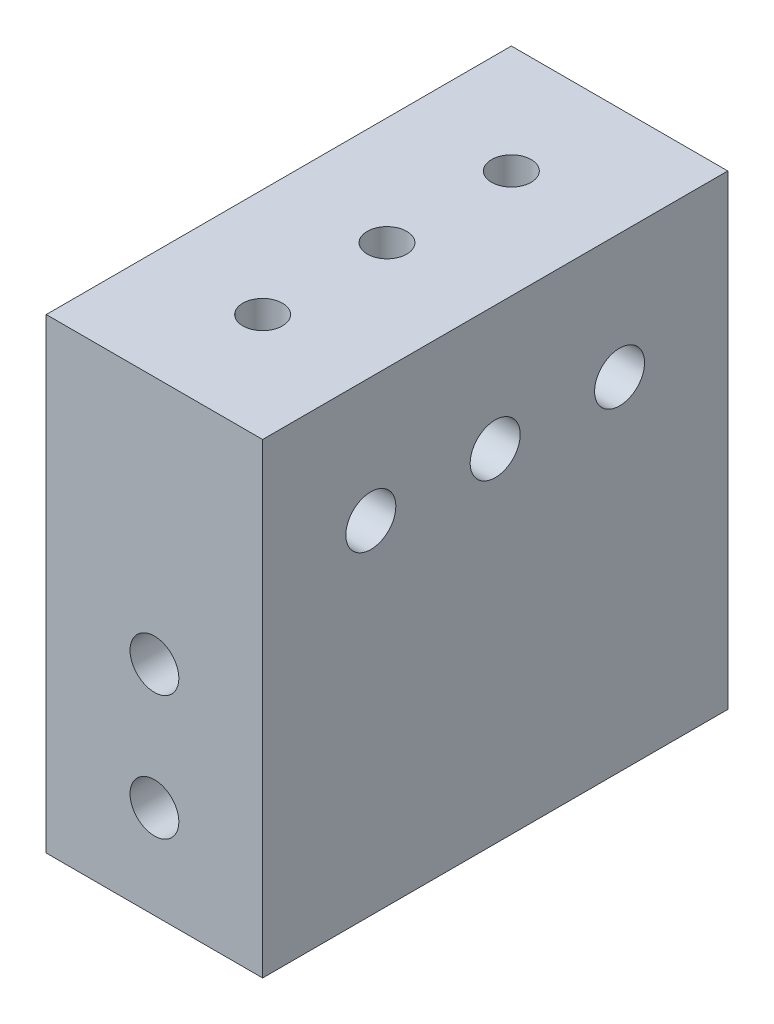
SolidWorks part; units mm, degrees
other "Markup1"
sketch "Sketch3" plane through (12.6365, 38.1, -23.749) normal (0.9027, 0.4189, -0.0984) x (-0.0151, -0.1977, -0.9801)
sketch "Sketch7" plane through (11.049, 23.8125, -23.749) normal (0.9027, 0.4189, -0.0984) x (-0.0151, -0.1977, -0.9801)
sketch "Sketch9" plane through (11.049, 23.8125, -23.749) normal (0.9027, 0.4189, -0.0984) x (-0.0151, -0.1977, -0.9801)
sketch "Sketch12" plane through (11.049, 23.8125, -23.749) normal (0.9027, 0.4189, -0.0984) x (-0.0151, -0.1977, -0.9801)
other "Markup2"
sketch "Sketch4" plane through (12.6365, 38.1, -23.749) normal (0.9027, 0.4189, -0.0984) x (-0.0151, -0.1977, -0.9801)
sketch "Sketch8" plane through (11.049, 23.8125, -23.749) normal (0.9027, 0.4189, -0.0984) x (-0.0151, -0.1977, -0.9801)
sketch "Sketch10" plane through (11.049, 23.8125, -23.749) normal (0.9027, 0.4189, -0.0984) x (-0.0151, -0.1977, -0.9801)
sketch "Sketch13" plane through (11.049, 23.8125, -23.749) normal (0.9027, 0.4189, -0.0984) x (-0.0151, -0.1977, -0.9801)
other "Markup3"
sketch "Sketch11" plane through (11.049, 23.8125, -23.749) normal (1, 0.0033, -0.0037) x (-0.003, -0.1893, -0.9819)
sketch "Sketch14" plane through (11.049, 23.8125, -23.749) normal (1, 0.0033, -0.0037) x (-0.003, -0.1893, -0.9819)
material "Nylon 101"
ref_plane "Front Plane" through (0, 0, 0) normal (0, 0, 1) x (1, 0, 0)
ref_plane "Top Plane" through (0, 0, 0) normal (0, 1, 0) x (1, 0, 0)
ref_plane "Right Plane" through (0, 0, 0) normal (1, 0, 0) x (0, 0, -1)
sketch "Sketch1" plane through (0, 0, 0) normal (0, 1, 0) x (1, 0, 0)
  line L0 (-12.6365, 25.3365) -> (12.6365, 25.3365)
  line L1 (-11.049, -23.749) -> (11.049, -23.749)
  line L2 (-11.049, -23.749) -> (-11.049, 23.749)
  line L3 (-11.049, 23.749) -> (11.049, 23.749)
  line L4 (11.049, -23.749) -> (11.049, 23.749)
  line L5 (-11.049, -23.749) -> (11.049, 23.749) construction
  line L6 (-11.049, 23.749) -> (11.049, -23.749) construction
  line L7 (12.6365, -25.3365) -> (12.6365, 25.3365)
  line L8 (-12.6365, -25.3365) -> (12.6365, -25.3365)
  line L9 (-12.6365, -25.3365) -> (-12.6365, 25.3365)
  point P0 (0, 0)
  dimension "D1" = 22.098
  dimension "D2" = 47.498
  dimension "D3" = 1.5875
extrude "Boss-Extrude1" add sketch "Sketch1" along normal mid plane 47.625 contours L1 L4 L3 L2 region at (0, 0, 0)
sketch "Sketch2" plane through (11.049, 0, 0) normal (1, 0, 0) x (0, 0, -1)
  line L0 (-23.749, 23.8125) -> (23.749, 23.8125) construction
  line L4 (-25.4, -23.8125) -> (25.4, -23.8125) construction
  line L5 (-25.4, -23.8125) -> (-25.4, 23.8125) construction
  line L6 (-25.4, 23.8125) -> (25.4, 23.8125) construction
  line L7 (25.4, -23.8125) -> (25.4, 23.8125) construction
  line L8 (-25.4, -23.8125) -> (25.4, 23.8125) construction
  line L9 (-25.4, 23.8125) -> (25.4, -23.8125) construction
  circle A0 centre (-12.7, 11.1125) radius 2.5527
  circle A1 centre (0, 11.1125) radius 2.5527
  circle A2 centre (12.7, 11.1125) radius 2.5527
  point P6 (0, 0)
  dimension "D1" = 5.1054
  dimension "D2" = 50.8
  dimension "D4" = 25.4
  dimension "D5" = 12.7
  dimension "D6" = 38.1
  dimension "D7" = 12.7
  dimension "D8" = 12.7
  dimension "D9" = 12.7
extrude "Cut-Extrude1" cut sketch "Sketch2" against normal through all
sketch "Sketch5" plane through (0, 0, -23.749) normal (0, 0, -1) x (-1, 0, 0)
  line L0 (11.049, 23.8125) -> (-11.049, 23.8125) construction
  line L1 (-12.7, -23.8125) -> (12.7, -23.8125) construction
  line L2 (-12.7, -23.8125) -> (-12.7, 23.8125) construction
  line L3 (-12.7, 23.8125) -> (12.7, 23.8125) construction
  line L4 (12.7, -23.8125) -> (12.7, 23.8125) construction
  line L5 (-12.7, -23.8125) -> (12.7, 23.8125) construction
  line L6 (-12.7, 23.8125) -> (12.7, -23.8125) construction
  circle A0 centre (0, -1.5875) radius 2.4892
  circle A2 centre (0, -14.2875) radius 2.4892
  point P0 (0, 0)
  dimension "D5" = 38.1
  dimension "D7" = 4.9784
  dimension "D8" = 4.9784
  dimension "D1" = 25.4
  dimension "D3" = 25.4
  dimension "D4" = 12.7
  dimension "D6" = 12.7
extrude "Cut-Extrude2" cut sketch "Sketch5" against normal through all
sketch "Sketch6" plane through (0, 23.8125, 0) normal (0, 1, 0) x (1, 0, 0)
  line L1 (11.049, -23.749) -> (11.049, 23.749) construction
  circle A0 centre (0, 0) radius 2.0193
  circle A1 centre (0, 12.7) radius 2.0193
  circle A2 centre (0, -12.7) radius 2.0193
  dimension "D3" = 4.0386
  dimension "D1" = 12.7
  dimension "D2" = 12.7
  dimension "D4" = 11.049
  dimension "D5" = 11.049
extrude "Cut-Extrude3" cut sketch "Sketch6" against normal blind 6.35
